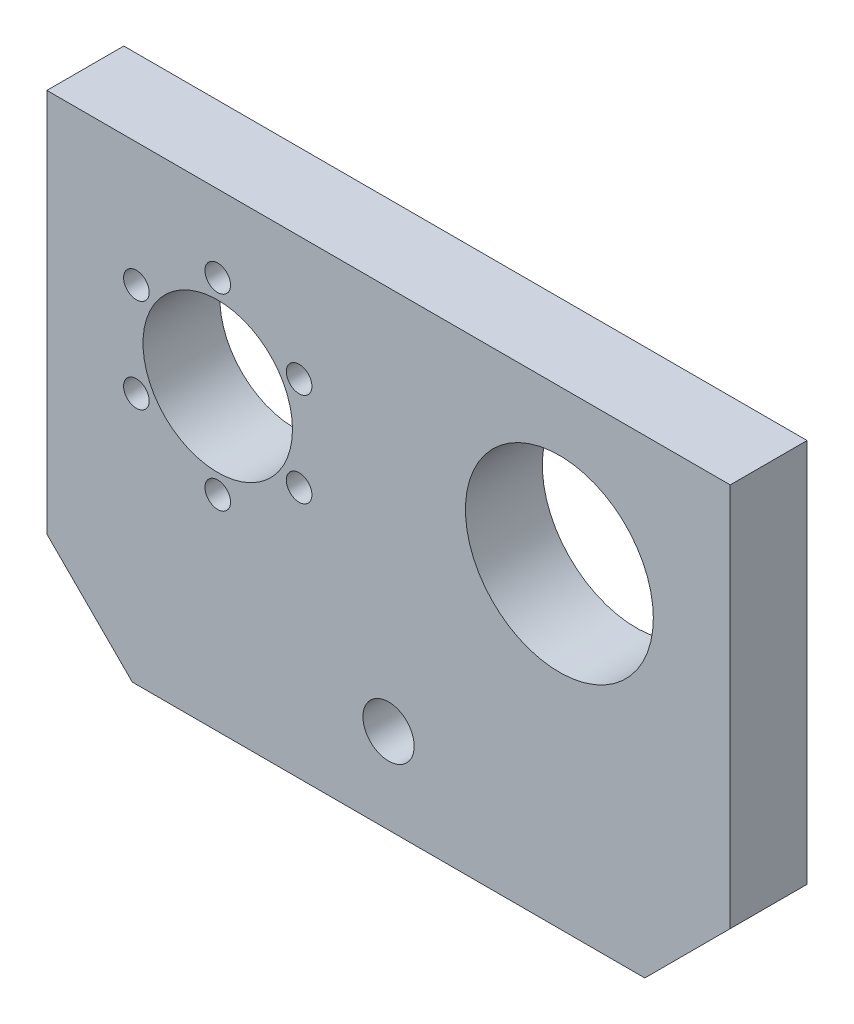
SolidWorks part; units mm, degrees
ref_plane "Front" through (0, 0, 0) normal (0, 0, 1) x (1, 0, 0)
ref_plane "Top" through (0, 0, 0) normal (0, 1, 0) x (1, 0, 0)
ref_plane "Right" through (0, 0, 0) normal (1, 0, 0) x (0, 0, -1)
sketch "Esquisse1" plane through (0, 0, 0) normal (0, 0, 1) x (1, 0, 0)
  line L1 (0, 0) -> (80, 0)
  line L2 (0, 0) -> (0, 55)
  line L3 (0, 55) -> (80, 55)
  line L4 (80, 0) -> (80, 55)
  dimension "D1" = 55
  dimension "D2" = 80
extrude "Boss.-Extru.1" add sketch "Esquisse1" along normal blind 9
sketch "Esquisse2" plane through (0, 0, 9) normal (0, 0, 1) x (1, 0, 0)
  line L0 (60, 55) -> (60, 0) construction
  line L1 (80, 55) -> (0, 55) construction
  line L2 (0, 0) -> (80, 0) construction
  line L3 (80, 0) -> (80, 55) construction
  line L4 (20, 35) -> (20, 55) construction
  line L5 (0, 55) -> (0, 0) construction
  circle A0 centre (60, 37) radius 11
  circle A1 centre (20, 35) radius 8.75
  circle A2 centre (20, 46) radius 1.5
  circle A3 centre (29.5263, 40.5) radius 1.5
  circle A4 centre (29.5263, 29.5) radius 1.5
  circle A5 centre (20, 24) radius 1.5
  circle A6 centre (10.4737, 29.5) radius 1.5
  circle A7 centre (10.4737, 40.5) radius 1.5
  point P18 (7.7118, 28.6521)
  point P19 (20, 20)
  point P29 (20, 35)
  dimension "D1" = 22
  dimension "D2" = 18
  dimension "D4" = 17.5
  dimension "D7" = 3
  dimension "D3" = 20
  dimension "D5" = 20
  dimension "D6" = 20
  dimension "D8" = 11
  dimension "D9" = 6
extrude "Enlèv. mat.-Extru.1" cut sketch "Esquisse2" against normal through all
sketch "Esquisse3" plane through (0, 0, 9) normal (0, 0, 1) x (1, 0, 0)
  circle A0 centre (40, 10) radius 3
  circle A1 centre (20, 35) radius 8.75 construction
  dimension "D3" = 6
  dimension "D1" = 25
  dimension "D2" = 20
extrude "Enlèv. mat.-Extru.2" cut sketch "Esquisse3" against normal through all
chamfer "Chanfrein1" distance 10 angle 45 2 edges at (80, 0, 4.5) (0, 0, 4.5)
